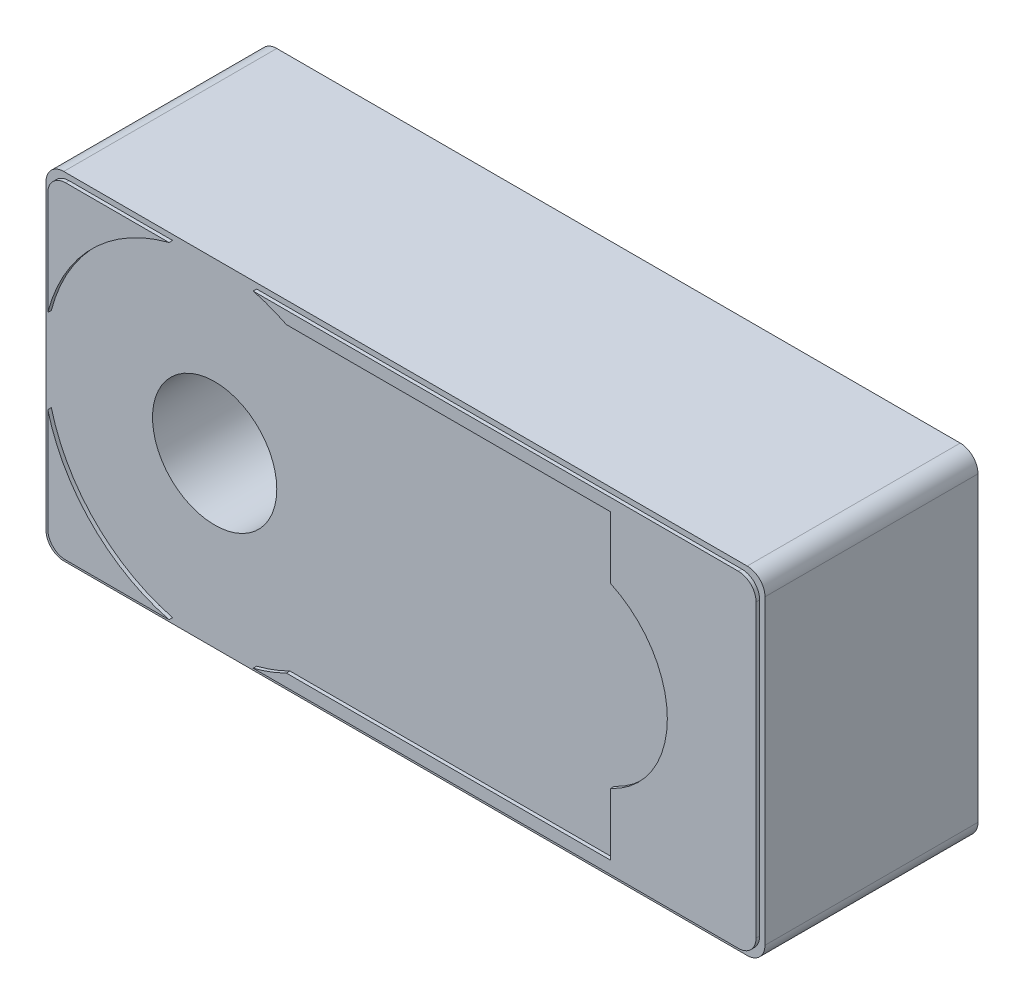
SolidWorks part; units mm, degrees
material "Acrílico (Impacto medio-alto)"
ref_plane "Alzado" through (0, 0, 0) normal (0, 0, 1) x (1, 0, 0)
ref_plane "Planta" through (0, 0, 0) normal (0, 1, 0) x (1, 0, 0)
ref_plane "Vista lateral" through (0, 0, 0) normal (1, 0, 0) x (0, 0, -1)
sketch "Croquis1" plane through (0, 0, 0) normal (0, 0, 1) x (1, 0, 0)
  line L0 (-9.5, 8.5) -> (-9.5, -8.5)
  line L1 (-8.5, -9.5) -> (30, -9.5)
  line L2 (31, -8.5) -> (31, 8.5)
  line L3 (30, 9.5) -> (-8.5, 9.5)
  line L7 (10.75, -9.5) -> (10.75, 9.5) construction
  line L8 (-9.5, 0) -> (31, 0) construction
  circle A0 centre (0, 0) radius 3.5
  arc A1 (31, 8.5) -> (30, 9.5) centre (30, 8.5) ccw
  arc A2 (30, -9.5) -> (31, -8.5) centre (30, -8.5) ccw
  arc A3 (-9.5, 8.5) -> (-8.5, 9.5) centre (-8.5, 8.5) cw
  arc A4 (-9.5, -8.5) -> (-8.5, -9.5) centre (-8.5, -8.5) ccw
  circle A5 centre (29.4, -7.9) radius 0.8
  circle A6 centre (-7.9, -7.9) radius 0.8
  circle A7 centre (-7.9, 7.9) radius 0.8
  circle A8 centre (29.4, 7.9) radius 0.8
  point P7 (-9.5, 0)
  point P8 (10.75, -9.5)
  point P9 (31, 0)
  point P10 (10.75, 9.5)
  point P15 (31, -9.5)
  point P16 (-3.5, 0)
  point P19 (-9.5, 9.5)
  point P22 (-9.5, -9.5)
  dimension "D3" = 7
  dimension "D5" = 1
  dimension "D8" = 1.6
  dimension "D6" = 1.6
  dimension "D1" = 19
  dimension "D2" = 40.5
  dimension "D4" = 6
  dimension "D7" = 1.6
extrude "Saliente-Extruir1" add sketch "Croquis1" along normal blind 12 contours L0 A4 L1 A2 L2 A1 L3 A3 A0 region at (11.3229, 0, 0)
sketch "Croquis2" plane through (0, 0, 12) normal (0, 0, 1) x (1, 0, 0)
  line L0 (29.7, -9.2) -> (-8.2, -9.2)
  line L1 (-9.2, -8.2) -> (-9.2, 8.2)
  line L2 (-8.2, 9.2) -> (29.7, 9.2)
  line L3 (30.7, 8.2) -> (30.7, -8.2)
  line L8 (22.5, 8.5) -> (22.5, -8.5)
  line L9 (22.5, -8.5) -> (4.2426, -8.5)
  line L10 (22.5, 8.5) -> (4.2426, 8.5)
  line L11 (31, -8.5) -> (31, 8.5) construction
  line L12 (-8.5, -9.5) -> (30, -9.5) construction
  line L13 (-9.5, 8.5) -> (-9.5, -8.5) construction
  line L14 (30, 9.5) -> (-8.5, 9.5) construction
  circle A0 centre (0, 0) radius 9.5
  arc A1 (-8.2, -9.2) -> (-9.2, -8.2) centre (-8.2, -8.2) cw
  arc A2 (-9.2, 8.2) -> (-8.2, 9.2) centre (-8.2, 8.2) cw
  arc A3 (29.7, 9.2) -> (30.7, 8.2) centre (29.7, 8.2) cw
  arc A4 (29.7, -9.2) -> (30.7, -8.2) centre (29.7, -8.2) ccw
  arc A5 (22.5, -5) -> (22.5, 5) centre (20.1938, 0) ccw
  point P23 (22.5, 0)
  point P27 (22.5, 5)
  point P28 (25.7, 0)
  point P34 (22.5, -5)
  circle M41 centre (-7.9, -7.9) radius 0.8
  circle M42 centre (29.4, -7.9) radius 0.8
  circle M43 centre (-7.9, 7.9) radius 0.8
  circle M44 centre (29.4, 7.9) radius 0.8
  dimension "D5" = 1
  dimension "D1" = 0.3
  dimension "D2" = 0.3
  dimension "D3" = 0.3
  dimension "D4" = 0.3
  dimension "D6" = 32
  dimension "D7" = 17
  dimension "D8" = 35.2
  dimension "D9" = 10
extrude "Saliente-Extruir2" add sketch "Croquis2" along normal blind 0.2 contours A1 L0 A0 L1 | L0 A4 L3 A3 L2 A0 | A2 L1 A0 L2 | M41 | M43 | M42 | M44 region at (16.0343, -8.8622, 12) region at (-7.2574, -7.2574, 12) region at (-7.2574, 7.2574, 12) region at (-7.9, -7.9, 12) region at (29.4, -7.9, 12) region at (-7.9, 7.9, 12) region at (29.4, 7.9, 12)
sketch "Croquis5"
  circle A0 centre (0, 0) radius 3.5
  circle A1 centre (0, 0) radius 6.05
  circle A2 centre (0, 0) radius 5.05
  dimension "D1" = 7
  dimension "D2" = 10.1
  dimension "D3" = 12.1
sketch "Croquis5<3>" plane through (0, 0, 0) normal (0, 0, 1) x (1, 0, 0) same geometry as "Croquis5"
shell "Vaciado6" thickness 1 removed face at (-7.1, -7.9, 0)
